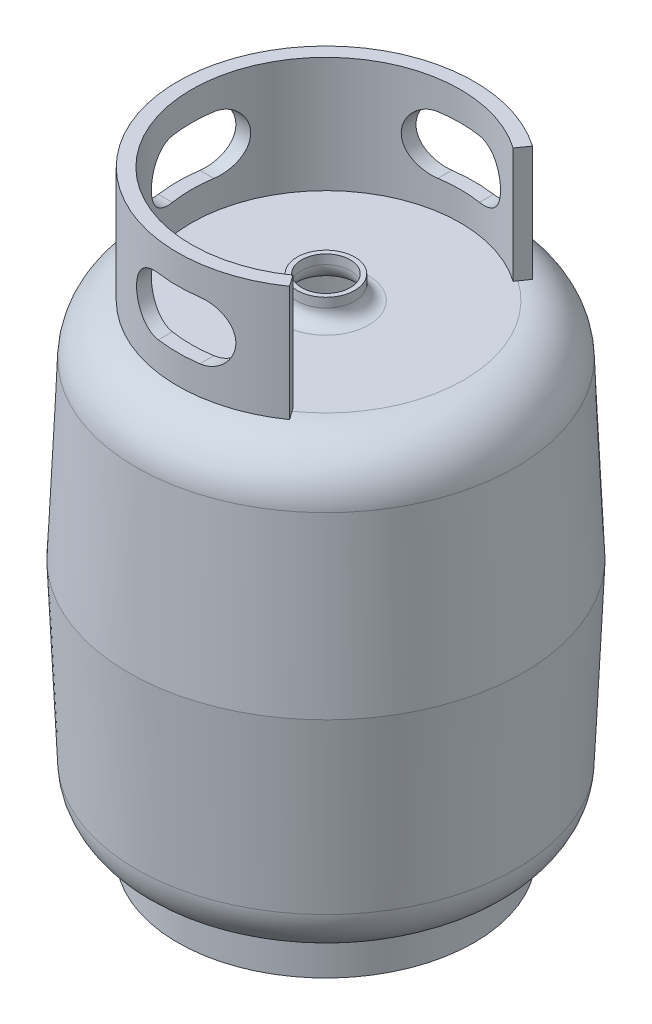
SolidWorks part; units mm, degrees
material "1060 Alloy"
ref_plane "Front Plane" through (0, 0, 0) normal (0, 0, 1) x (1, 0, 0)
ref_plane "Top Plane" through (0, 0, 0) normal (0, 1, 0) x (1, 0, 0)
ref_plane "Right Plane" through (0, 0, 0) normal (1, 0, 0) x (0, 0, -1)
sketch "Sketch1" plane through (0, 0, 0) normal (0, 0, 1) x (1, 0, 0)
  line L0 (0, -179.2118) -> (0, 179.2118) construction
  line L1 (-193.9008, 0) -> (193.9008, 0) construction
  line L2 (0, 213.75) -> (-25, 213.75)
  line L3 (-25, 213.75) -> (-25, 205.75)
  line L4 (-37, 193.75) -> (-119.4219, 193.75)
  line L5 (-164.379, 150.7129) -> (-170.9593, 0)
  line L6 (-170.9593, 0) -> (-164.379, -150.7129)
  line L7 (-119.4219, -193.75) -> (0, -193.75)
  line L8 (0, 213.75) -> (0, -193.75)
  arc A0 (-164.379, 150.7129) -> (-119.4219, 193.75) centre (-119.4219, 148.75) cw
  arc A1 (-119.4219, -193.75) -> (-164.379, -150.7129) centre (-119.4219, -148.75) cw
  arc A2 (-37, 193.75) -> (-25, 205.75) centre (-37, 205.75) ccw
  point P4 (0, 0)
  point P8 (0, 0)
  point P17 (-162.5, 193.75)
  point P20 (-162.5, -193.75)
  point P23 (-25, 193.75)
  dimension "D8" = 45
  dimension "D9" = 12
  dimension "D1" = 25
  dimension "D2" = 162.5
  dimension "D3" = 162.5
  dimension "D4" = 193.75
  dimension "D5" = 193.75
  dimension "D6" = 20
  dimension "D7" = 92.5
revolve "Revolve1" add sketch "Sketch1" angle 360 about L8
shell "Shell1" thickness 4 removed face at (-25, 213.75, 0)
sketch "Sketch2" plane through (0, 193.75, 0) normal (0, 1, 0) x (1, 0, 0)
  line L0 (0, -194.2129) -> (0, 194.2129) construction
  line L1 (-245.2833, 0) -> (245.2833, 0) construction
  line L2 (0, 0) -> (73.6598, 105.197)
  line L3 (0, 0) -> (73.6598, -105.197)
  arc A0 (73.6598, 105.197) -> (73.6598, -105.197) centre (0, 0) ccw
  arc A1 (66.7768, 95.3672) -> (66.7768, -95.3672) centre (0, 0) ccw
  circle A2 centre (0, 0) radius 119.4219 construction
  point P9 (0, 0)
  point P12 (0, 0)
  circle M4 centre (0, 0) radius 119.4219
  dimension "D1" = 3
  dimension "D2" = 12
  dimension "D3" = 55
extrude "Boss-Extrude1" add sketch "Sketch2" along normal blind 100 contours L2 A0 L3 M4 | A1 L2 L3 M4 region at (-116.7258, 193.75, 0) region at (-122.69, 193.75, 0)
sketch "Sketch3" plane through (0, 0, 0) normal (0, 0, 1) x (1, 0, 0)
  line L0 (0, -321.6688) -> (0, 321.6688) construction
  line L1 (-18, 268.75) -> (18, 268.75)
  line L2 (-18, 218.75) -> (18, 218.75)
  line L5 (73.6598, 293.75) -> (-128.4219, 293.75) construction
  arc A0 (18, 218.75) -> (18, 268.75) centre (18, 243.75) ccw
  arc A1 (-18, 218.75) -> (-18, 268.75) centre (-18, 243.75) cw
  point P4 (0, 0)
  point P6 (43, 243.75)
  point P8 (-43, 243.75)
  dimension "D1" = 50
  dimension "D3" = 50
  dimension "D2" = 86
extrude "Cut-Extrude1" cut sketch "Sketch3" against normal blind 251 and the other way blind 203
sketch "Sketch5" plane through (0, 0, 0) normal (1, 0, 0) x (0, 0, -1)
  line L0 (-18, 243.75) -> (18, 243.75) construction
  line L1 (-18, 268.75) -> (18, 268.75)
  line L2 (-18, 218.75) -> (18, 218.75)
  line L3 (0, 293.75) -> (0, 193.75) construction
  line L4 (116.4219, 293.75) -> (-116.4219, 293.75) construction
  arc A0 (-18, 268.75) -> (-18, 218.75) centre (-18, 243.75) ccw
  arc A1 (18, 218.75) -> (18, 268.75) centre (18, 243.75) ccw
  point P2 (0, 243.75)
  point P7 (-43, 243.75)
  point P8 (43, 243.75)
  dimension "D2" = 50
  dimension "D1" = 86
  dimension "D3" = 50
extrude "Cut-Extrude2" cut sketch "Sketch5" against normal blind 251
sketch "Sketch6" plane through (0, -193.75, 0) normal (0, -1, 0) x (1, 0, 0)
  circle A0 centre (0, 0) radius 128.4219
  circle A1 centre (0, 0) radius 116.4219
  circle A2 centre (0, 0) radius 119.4219 construction
  dimension "D1" = 3
  dimension "D2" = 12
extrude "Boss-Extrude2" add sketch "Sketch6" along normal blind 30
